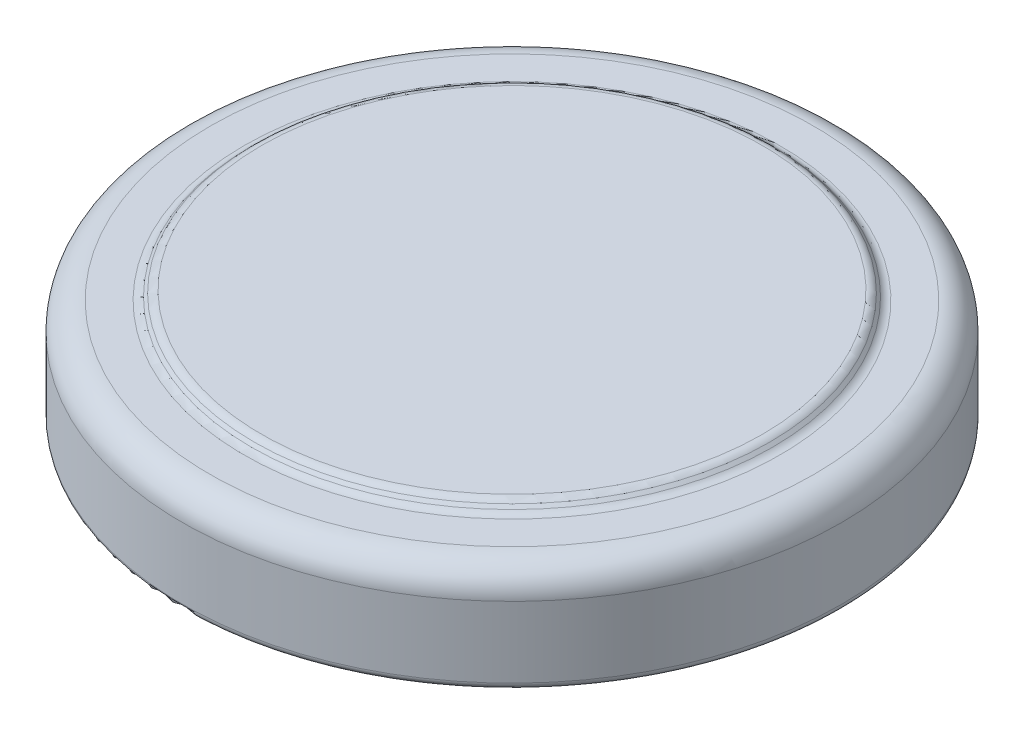
SolidWorks part; units mm, degrees
ref_plane "Front Plane" through (0, 0, 0) normal (0, 0, 1) x (1, 0, 0)
ref_plane "Top Plane" through (0, 0, 0) normal (0, 1, 0) x (1, 0, 0)
ref_plane "Right Plane" through (0, 0, 0) normal (1, 0, 0) x (0, 0, -1)
sketch "Sketch1" plane through (0, 0, 0) normal (0, 0, 1) x (1, 0, 0)
  line L0 (0, 0) -> (-4.65, 0)
  line L1 (-4.75, 0.1) -> (-4.75, 1.12)
  line L2 (-3.6079, 1.65) -> (0, 1.65)
  line L3 (0, 1.65) -> (0, 0)
  line L4 (-3.7561, 1.5639) -> (-3.7139, 1.6061)
  line L7 (-3.8621, 1.52) -> (-4.35, 1.52)
  arc A0 (-4.75, 1.12) -> (-4.35, 1.52) centre (-4.35, 1.12) cw
  arc A1 (-3.6079, 1.65) -> (-3.7139, 1.6061) centre (-3.6079, 1.5) ccw
  arc A2 (-3.8621, 1.52) -> (-3.7561, 1.5639) centre (-3.8621, 1.67) ccw
  arc A3 (-4.65, 0) -> (-4.75, 0.1) centre (-4.65, 0.1) cw
  point P9 (-4.75, 1.52)
  point P13 (-3.8, 1.52)
  point P17 (-4.75, 0)
  point P18 (-3.8, 1.52)
  point P20 (-3.8, 1.52)
  dimension "D6" = 0.4
  dimension "D7" = 0.15
  dimension "D8" = 0.1
  dimension "D1" = 4.75
  dimension "D2" = 1.65
  dimension "D3" = 3.8
  dimension "D4" = 1.52
  dimension "D5" = 45
revolve "Revolve1" add sketch "Sketch1" angle 360 about L3
sketch "Sketch2" plane through (0, 0, 0) normal (0, -1, 0) x (1, 0, 0)
  line L0 (0.25, -0.25) -> (0.25, -2)
  line L1 (-0.25, 2) -> (0.25, 2)
  line L2 (-0.25, 2) -> (-0.25, 0.25)
  line L3 (-0.25, -2) -> (0.25, -2)
  line L4 (0.25, 2) -> (0.25, 0.25)
  line L5 (-2, 0.25) -> (-0.25, 0.25)
  line L6 (-2, 0.25) -> (-2, -0.25)
  line L7 (-2, -0.25) -> (-0.25, -0.25)
  line L8 (2, 0.25) -> (2, -0.25)
  line L9 (-0.25, -0.25) -> (-0.25, -2)
  line L10 (0.25, 0.25) -> (2, 0.25)
  line L11 (0.25, -0.25) -> (2, -0.25)
  circle A0 centre (0, 0) radius 3.25 construction
  text T0 "                          SR68" font "Century Gothic" height 1
  dimension "D1" = 6.5
  dimension "D2" = 0.25
  dimension "D3" = 4
  dimension "D4" = 0.5
  dimension "D5" = 0.5
  dimension "D6" = 0.25
  dimension "D7" = 4
  dimension "D8" = 2
  dimension "D9" = 2
wrap "Wrap1" sketch "Sketch2" wrap type scribe source sketch "Sketch2" face at (-4.65, 0, 0)
